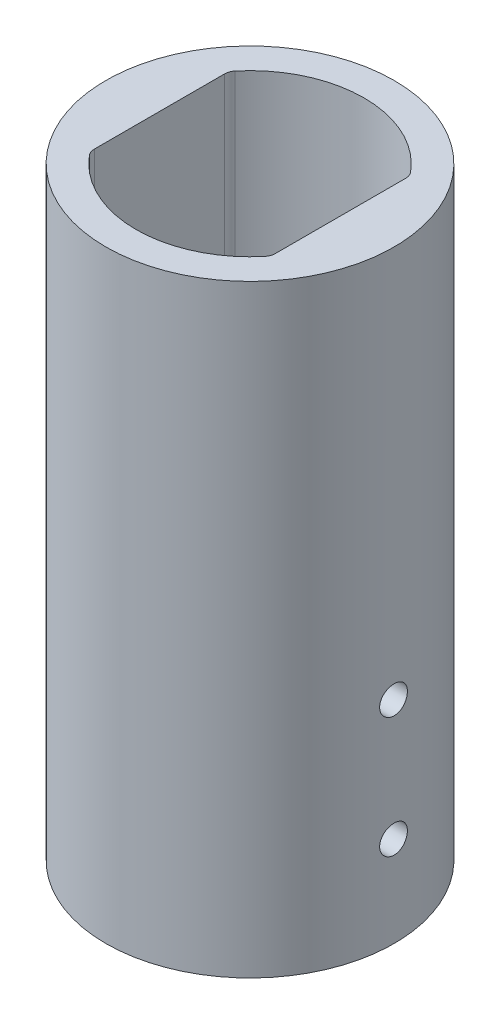
SolidWorks part; units mm, degrees
ref_plane "Front Plane" through (0, 0, 0) normal (0, 0, 1) x (1, 0, 0)
ref_plane "Top Plane" through (0, 0, 0) normal (0, 1, 0) x (1, 0, 0)
ref_plane "Right Plane" through (0, 0, 0) normal (1, 0, 0) x (0, 0, -1)
sketch "Sketch1" plane through (0, 0, 0) normal (0, 1, 0) x (1, 0, 0)
  line L0 (-15, 11.4983) -> (-15, -11.4983)
  line L1 (15, 11.4983) -> (15, -11.4983)
  circle A0 centre (0, 0) radius 23.9
  circle A1 centre (0, 0) radius 18.9
  dimension "D1" = 47.8
  dimension "D2" = 37.8
  dimension "D3" = 15
  dimension "D4" = 15
extrude "Boss-Extrude1" add sketch "Sketch1" along normal blind 100 contours A0 A1 | L0 A1 | L1 A1 region at (-16.5747, 0, 0) region at (16.5747, 0, 0) region at (-23.224, 0, 0)
sketch "Sketch2" plane through (0, 0, 0) normal (1, 0, 0) x (0, 0, -1)
  circle A0 centre (0, 15) radius 2.3
  circle A1 centre (0, 35) radius 2.3
  dimension "D3" = 15
  dimension "D1" = 4.6
  dimension "D2" = 4.6
  dimension "D4" = 20
extrude "Cut-Extrude1" cut sketch "Sketch2" against normal through all both and the other way through all
fillet "Fillet1" radius 2 4 edges at (-15, 50, 11.4983) (-15, 50, -11.4983) (15, 50, 11.4983) (15, 50, -11.4983)
equation "\"D1@Sketch1\"=\"TubeInnerDiameter\""
equation "\"TubeInnerDiameter\"= 47.8"
equation "\"ReleaseMechanisumHeight\"=100"
equation "\"WireDiameter\"=3.38983"
equation "\"servoHoleDiameter\" = 2.8"
equation "\"CordDiameter\"= 5"
equation "\"MountingBoldDiameter\"=2.8"
equation "\"D2@Sketch1\"=\"TubeInnerDiameter\"-10"
equation "\"D1@Boss-Extrude1\"=\"ReleaseMechanisumHeight\""
equation "\"TubeMountingBoltDiameter\" = 5"
equation "\"D1@Sketch2\"=\"TubeMountingBoltDiameter\"-0.4"
equation "\"D2@Sketch2\"=\"TubeMountingBoltDiameter\"-0.4"
